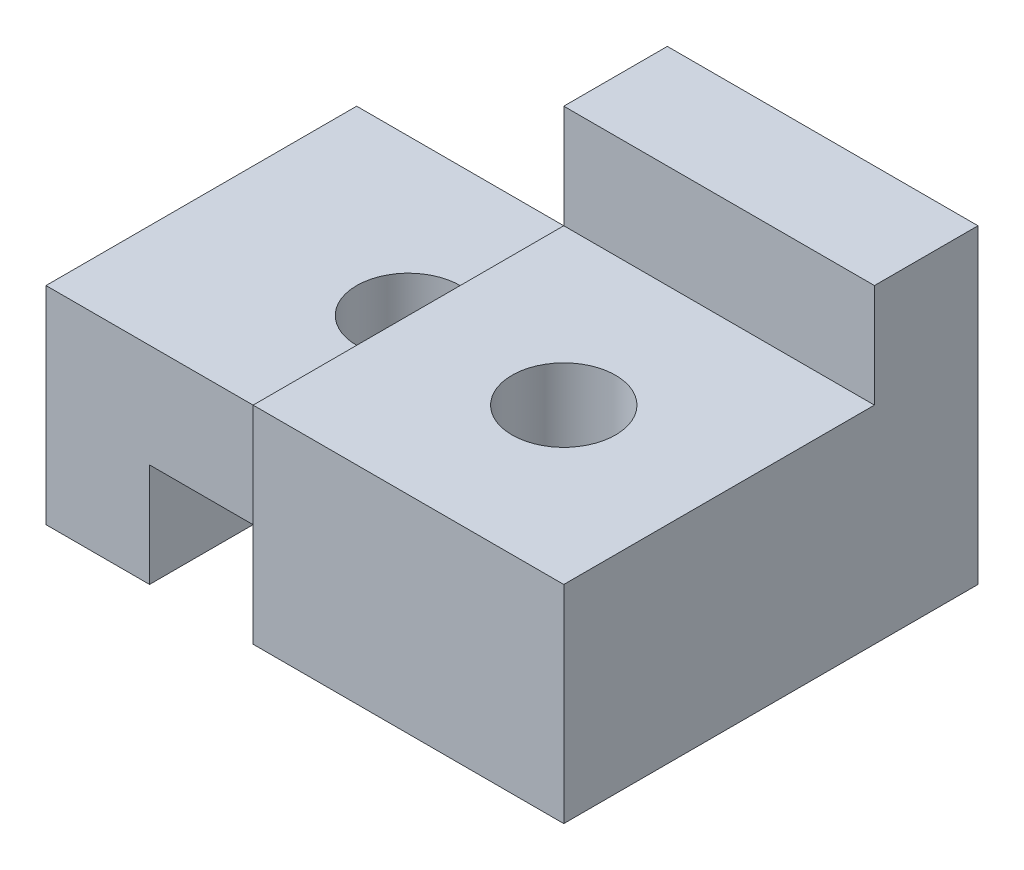
SolidWorks part; units mm, degrees
ref_plane "Front Plane" through (0, 0, 0) normal (0, 0, 1) x (1, 0, 0)
ref_plane "Top Plane" through (0, 0, 0) normal (0, 1, 0) x (1, 0, 0)
ref_plane "Right Plane" through (0, 0, 0) normal (1, 0, 0) x (0, 0, -1)
sketch "Sketch1" plane through (0, 0, 0) normal (0, 0, 1) x (1, 0, 0)
  line L0 (0, 0) -> (25.4, 0)
  line L1 (25.4, 0) -> (25.4, 25.4)
  line L2 (25.4, 25.4) -> (152.4, 25.4)
  line L3 (152.4, 25.4) -> (152.4, 101.6)
  line L4 (152.4, 101.6) -> (76.2, 101.6)
  line L5 (76.2, 101.6) -> (76.2, 50.8)
  line L6 (76.2, 50.8) -> (0, 50.8)
  line L7 (0, 50.8) -> (0, 0)
  line L8 (76.2, 50.8) -> (76.2, 25.4)
  line L9 (76.2, 76.2) -> (152.4, 76.2)
  dimension "D1" = 50.8
  dimension "D2" = 25.4
  dimension "D3" = 25.4
  dimension "D4" = 76.2
  dimension "D5" = 76.2
  dimension "D6" = 152.4
extrude "Boss-Extrude1" add sketch "Sketch1" along normal blind 76.2 contours L8 L6 L7 L0 L1 L2 region at (31.75, 31.75, 0)
extrude "Boss-Extrude2" add sketch "Sketch1<13>" along normal blind 101.6 contours L9 L5 L8 L2 L3 region at (114.3, 50.8, 0)
sketch "Sketch1<13>" plane through (0, 0, 0) normal (0, 0, 1) x (1, 0, 0) same geometry as "Sketch1"
extrude "Boss-Extrude3" add sketch "Sketch1<14>" along normal blind 25.4 contours L5 L9 L3 L4 region at (114.3, 88.9, 0)
sketch "Sketch1<14>" plane through (0, 0, 0) normal (0, 0, 1) x (1, 0, 0) same geometry as "Sketch1"
sketch "Sketch3" plane through (0, 50.8, 0) normal (0, 1, 0) x (1, 0, 0)
  line L0 (0, -76.2) -> (0, 0) construction
  line L1 (76.2, 0) -> (0, 0) construction
  line L2 (152.4, -101.6) -> (152.4, -25.4) construction
  line L3 (152.4, 0) -> (76.2, 0) construction
  line L4 (76.2, -101.6) -> (152.4, -101.6) construction
  line L5 (76.2, -76.2) -> (0, -76.2) construction
  line L6 (152.4, -25.4) -> (152.4, 0) construction
  circle A0 centre (50.8, -38.1) radius 12.7
  circle A1 centre (114.3, -63.5) radius 12.7
  point P4 (0, 0)
  point P19 (0, 0)
  point P20 (0, 0)
  dimension "D3" = 25.4
  dimension "D4" = 63.5
  dimension "D7" = 25.4
  dimension "D1" = 50.8
  dimension "D2" = 38.1
  dimension "D5" = 38.1
  dimension "D6" = 101.6
  dimension "D8" = 76.2
extrude "Cut-Extrude2" cut sketch "Sketch3" against normal blind 25.4 contours A0
sketch "Sketch4" plane through (0, 76.2, 0) normal (0, 1, 0) x (1, 0, 0)
  line L0 (152.4, -101.6) -> (152.4, -25.4) construction
  line L2 (152.4, 0) -> (76.2, 0) construction
  circle A0 centre (114.3, -63.5) radius 12.7
  point P2 (120.8823, -74.5149)
  dimension "D3" = 25.4
  dimension "D1" = 38.1
  dimension "D2" = 63.5
extrude "Cut-Extrude4" cut sketch "Sketch4" against normal blind 50.8 contours A0
